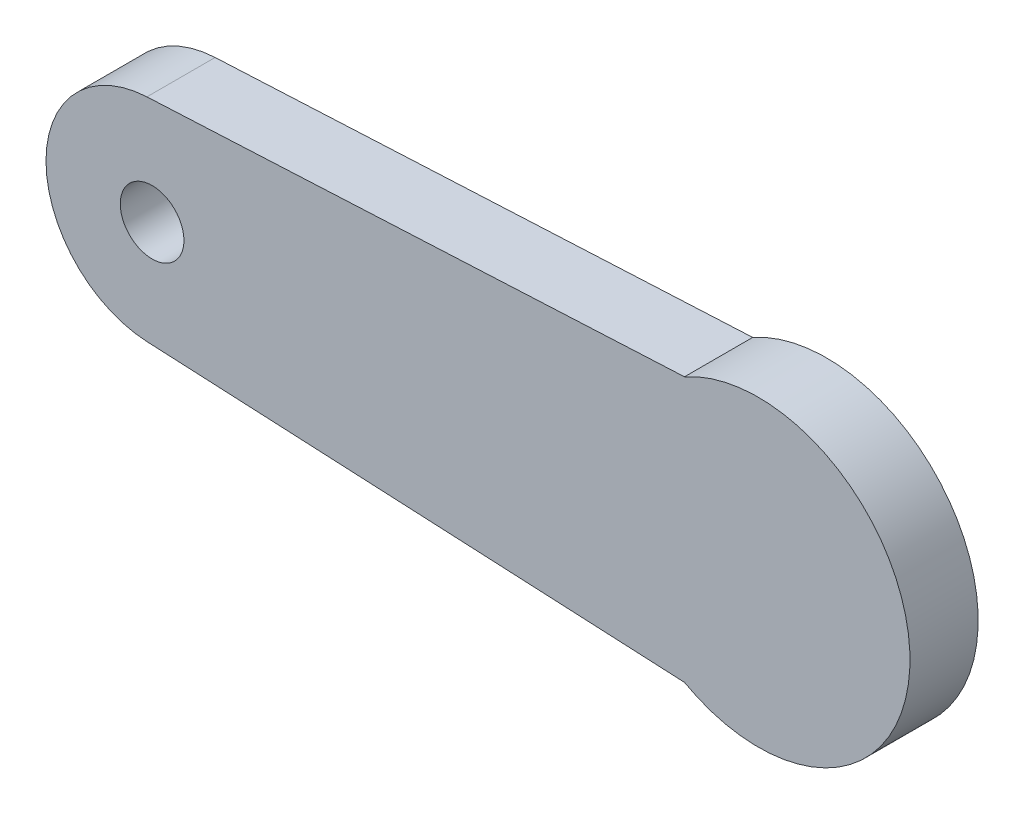
SolidWorks part; units mm, degrees
ref_plane "Front Plane" through (0, 0, 0) normal (0, 0, 1) x (1, 0, 0)
ref_plane "Top Plane" through (0, 0, 0) normal (0, 1, 0) x (1, 0, 0)
ref_plane "Right Plane" through (0, 0, 0) normal (1, 0, 0) x (0, 0, -1)
sketch "Sketch1" plane through (0, 0, 0) normal (0, 0, 1) x (1, 0, 0)
  line L0 (-20, 0) -> (20, 0)
  line L1 (0, -55) -> (0, 55) construction
  line L2 (-16, 3) -> (16, 3)
  line L3 (-16, -3) -> (16, -3)
  circle A0 centre (20, 0) radius 5
  circle A1 centre (-20, 0) radius 5
  point P4 (0, 0)
  point P12 (0, 3)
extrude "Boss-Extrude1" add sketch "Sketch1" along normal mid plane 4 contours A1 | L2 A1 L0 A0 | L0 A1 L3 A0 | A0 region at (0, 1.5159, 0) region at (-15.3907, -1.5364, 0) region at (0, -1.5159, 0) region at (15.3907, 1.5364, 0)
ref_axis "Axis1" through (20, 0, 7.1802) along (0, 0, -1)
ref_axis "Axis2" through (-20, 0, 11.9632) along (0, 0, -1)
sketch "Sketch3" plane through (0, 0, 2) normal (0, 0, 1) x (1, 0, 0)
  line L0 (-20.3428, -6.9916) -> (15.1242, -8.7308)
  line L1 (2.2, 0) -> (-2.2, 0) construction
  line L2 (-20.3428, 6.9916) -> (15.1242, 8.7308)
  circle A0 centre (20, 0) radius 10
  circle A1 centre (-20, 0) radius 7
  arc M4 (16, -3) -> (16, 3) centre (20, 0) ccw
  line M5 (16, 3) -> (-16, 3)
  arc M6 (-16, 3) -> (-16, -3) centre (-20, 0) ccw
  line M7 (-16, -3) -> (16, -3)
extrude "Boss-Extrude2" add sketch "Sketch3" against normal up to surface (4 mm away) contours A1 M5 M7 M6 | A1 A0 L2 M5 | A0 M5 M4 M7 | A0 M5 M7 M4 | A1 A0 M7 M5 | A1 L0 A0 M7 | A1 M7 M5 M6 region at (-1.0865, -5.6076, 2) region at (-26.8067, 0, 2) region at (12.4606, -6.1354, 2) region at (-1.0865, 5.6076, 2) region at (-19.2099, 0, 2) region at (-1.5347, 0, 2) region at (17.946, 0, 2) up to face at (0, 0, -2)
sketch "Sketch4" plane through (0, 0, 2) normal (0, 0, 1) x (1, 0, 0)
  line L0 (20, 0) -> (-4, 0)
ref_axis "Axis3" through (-4, 0, -14.3003) along (0, 0, 1)
sketch "Sketch5" plane through (0, 0, 2) normal (0, 0, 1) x (1, 0, 0)
  line L0 (-4, 3.5) -> (8, 3.5)
  line L1 (-4, -3.5) -> (8, -3.5)
  line L2 (2.2, 0) -> (-2.2, 0) construction
  line L3 (-4, -3.9) -> (8, -3.9)
  line L4 (-4, 3.9) -> (8, 3.9)
  arc A0 (15.6495, -5.9861) -> (15.6495, 5.9861) centre (20, 0) ccw
  arc A1 (-4, 3.5) -> (-4, -3.5) centre (-4, 0) ccw
  arc A2 (8, 3.5) -> (15.6495, 5.9861) centre (8, 16.5115) ccw
  arc A3 (8, -3.5) -> (15.6495, -5.9861) centre (8, -16.5115) cw
  arc A4 (-4, 3.9) -> (-4, -3.9) centre (-4, 0) ccw
  arc A5 (8, -3.9) -> (15.4144, -6.3097) centre (8, -16.5115) cw
  arc A6 (15.4144, -6.3097) -> (15.4144, 6.3097) centre (20, 0) ccw
  arc A7 (8, 3.9) -> (15.4144, 6.3097) centre (8, 16.5115) ccw
  dimension "D1" = 0.4
sketch "Sketch6" plane through (0, 0, -2) normal (0, 0, -1) x (-1, 0, 0)
  line L0 (-8, -3.5) -> (4, -3.5)
  line L1 (2.2, 0) -> (-2.2, 0) construction
  line L2 (-8, 3.5) -> (4, 3.5)
  line L3 (-8, 3.9) -> (4, 3.9)
  line L4 (-8, -3.9) -> (4, -3.9)
  arc A0 (-15.6495, 5.9861) -> (-15.6495, -5.9861) centre (-20, 0) ccw
  arc A1 (-8, -3.5) -> (-15.6495, -5.9861) centre (-8, -16.5115) ccw construction
  arc A2 (-15.6495, -5.9861) -> (-8, -3.5) centre (-8, -16.5115) cw
  arc A3 (4, -3.5) -> (4, 3.5) centre (4, 0) ccw
  arc A4 (4, -3.5) -> (4, 3.5) centre (4, 0) ccw construction
  arc A5 (-15.6495, 5.9861) -> (-8, 3.5) centre (-8, 16.5115) ccw
  arc A6 (4, -3.9) -> (4, 3.9) centre (4, 0) ccw
  arc A7 (-15.4144, 6.3097) -> (-8, 3.9) centre (-8, 16.5115) ccw
  arc A8 (-15.4144, 6.3097) -> (-15.4144, -6.3097) centre (-20, 0) ccw
  arc A9 (-15.4144, -6.3097) -> (-8, -3.9) centre (-8, -16.5115) cw
  dimension "D1" = 0.4
extrude "Cut-Extrude3" cut sketch "Sketch6" against normal blind 3.15 contours A5 L2 A3 L0 A2 A0
sketch "Sketch7" plane through (0, 0, 2) normal (0, 0, 1) x (1, 0, 0)
  line L0 (-20.3428, -6.9916) -> (15.1242, -8.7308)
  line L1 (-20.3428, -6.9916) -> (15.1242, -8.7308) construction
  line L2 (2.2, 0) -> (-2.2, 0) construction
  line L3 (-20.3428, 6.9916) -> (15.1242, 8.7308)
  circle A0 centre (20, 0) radius 10
  circle A1 centre (-20, 0) radius 7
  line M2 (-20.3428, -6.9916) -> (15.1242, -8.7308)
  arc M3 (15.1242, -8.7308) -> (15.1242, 8.7308) centre (20, 0) ccw
  line M4 (15.1242, 8.7308) -> (-20.3428, 6.9916)
  arc M5 (-20.3428, 6.9916) -> (-20.3428, -6.9916) centre (-20, 0) ccw
extrude "Boss-Extrude3" add sketch "Sketch7" along normal blind 0.5 contours A1 M5 | A1 A0 M2 M4 | A0 M3 region at (-1.239, 0, 2) region at (-20, 0, 2) region at (20, 0, 2)
sketch "Sketch8" plane through (0, 0, -2) normal (0, 0, -1) x (-1, 0, 0)
  circle A0 centre (20, 0) radius 2.1
extrude "Cut-Extrude4" cut sketch "Sketch8" against normal through all
